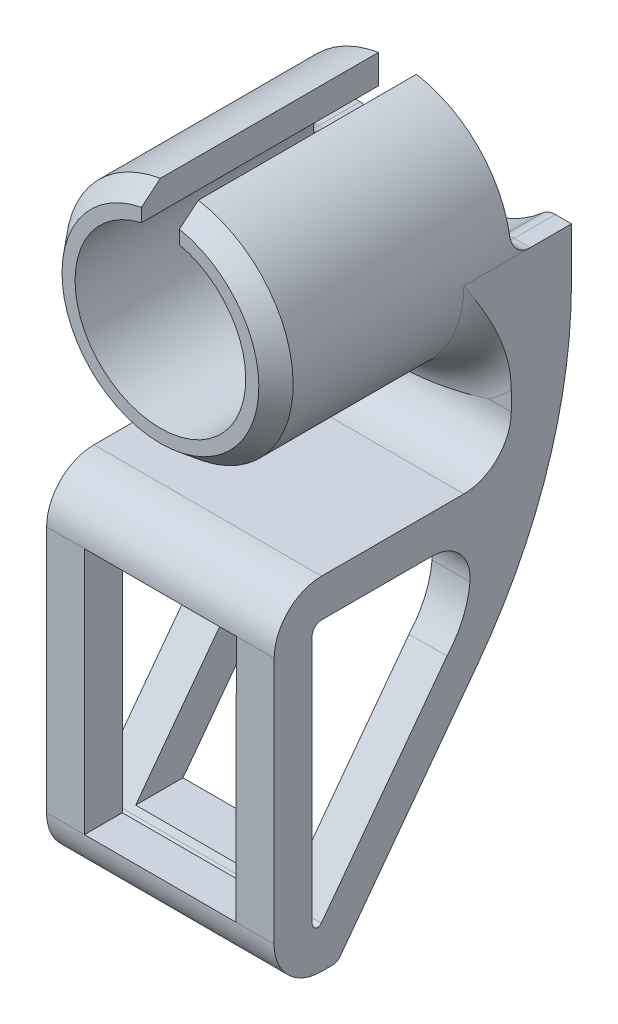
SolidWorks part; units mm, degrees
material "ABS PC"
ref_plane "Front Plane" through (0, 0, 0) normal (0, 0, 1) x (1, 0, 0)
ref_plane "Top Plane" through (0, 0, 0) normal (0, 1, 0) x (1, 0, 0)
ref_plane "Right Plane" through (0, 0, 0) normal (1, 0, 0) x (0, 0, -1)
sketch "Sketch1" plane through (0, 0, 0) normal (0, 0, 1) x (1, 0, 0)
  circle A0 centre (0, 0) radius 12
  dimension "D1" = 24
extrude "Boss-Extrude1" add sketch "Sketch1" along normal blind 25
sketch "Sketch2" plane through (0, 0, 25) normal (0, 0, 1) x (1, 0, 0)
  line L3 (-2, 12) -> (2, 12)
  line L7 (-2, 8.775) -> (-2, 12)
  line L10 (2, 8.775) -> (2, 12)
  arc A0 (-2, 8.775) -> (2, 8.775) centre (0, 0) ccw
  point P1 (0, 12)
  dimension "D1" = 18
  dimension "D4" = 4
  dimension "D6" = 12
extrude "Cut-Extrude1" cut sketch "Sketch2" against normal up to surface (25 mm away) up to face at (12, 0, 0)
sketch "Sketch3" plane through (0, 0, 0) normal (0, 0, -1) x (-1, 0, 0)
  line L0 (-9.5028, 0) -> (-12, 0)
  line L1 (9.5028, 0) -> (12, 0)
  line L2 (12, 0) -> (12, -19)
  line L3 (-12, 0) -> (-12, -19)
  line L4 (12, -19) -> (-12, -19)
  arc A0 (-9.5028, 0) -> (9.5028, 0) centre (0, 9.5) ccw
  circle A1 centre (0, 0) radius 12 construction
  point P11 (0, -3.937)
  dimension "D1" = 19
  dimension "D2" = 13.437
  dimension "D3" = 3.937
extrude "Boss-Extrude2" add sketch "Sketch3" along normal blind 6.35
fillet "Fillet1" radius 7.62 1 edges at (0, -9, 0)
fillet "Fillet2" [suppressed] radius 7.62
chamfer "Chamfer1" distance 2 angle 39 1 edges at (0, -12, 25) first distance on face at (0, 2.526, 8.3333)
sketch "Sketch6" plane through (0, -19, 0) normal (0, -1, 0) x (1, 0, 0)
  line L0 (-12, 25) -> (-12, -6.35)
  line L1 (-12, 25) -> (12, 25)
  line L2 (-12, -6.35) -> (12, -6.35)
  line L3 (12, 25) -> (12, -6.35)
  line L6 (10.3804, 25) -> (-10.3804, 25) construction
  point P1 (0, 0)
  point P9 (0, -6.35)
extrude "Boss-Extrude3" add sketch "Sketch6" along normal blind 3
sketch "Sketch7" plane through (12, 0, 0) normal (1, 0, 0) x (0, 0, -1)
  line L0 (-25, -22) -> (6.35, -22)
  line L2 (6.35, -22) -> (-18.3486, -55.1118)
  line L3 (-25.0132, -55.1118) -> (-18.3486, -55.1118)
  line L4 (-25, -22) -> (-25.0132, -55.1118)
extrude "Boss-Extrude4" add sketch "Sketch7" against normal up to surface (24 mm away) up to face at (-12, -13.6667, 6.2167)
fillet "Fillet3" radius 50 1 edges at (0, -22, -6.35)
fillet "Fillet7" radius 5 2 edges at (0, -19, 0) (0, -12, 0)
fillet "Fillet8" radius 5 1 edges at (0, -55.1118, 25.0132)
fillet "Fillet9" radius 5 1 edges at (0, -19, 25)
sketch "Sketch8" plane through (12, 0, 0) normal (1, 0, 0) x (0, 0, -1)
  line L29 (-5, -23) -> (-20.0008, -23)
  line L30 (-21.0008, -23.9996) -> (-21.0112, -50.1114)
  line L31 (-20.319, -51.0632) -> (-6.7779, -32.9096)
  line L32 (-5, -23) -> (-20.0008, -23)
  line L33 (-21.0008, -23.9996) -> (-21.0112, -50.1114)
  line L34 (-20.319, -51.0632) -> (-6.7779, -32.9096)
  arc A12 (-5, -23) -> (-6.7779, -32.9096) centre (-13.828, -26.5305) cw
  arc A16 (-20.0008, -23) -> (-21.0008, -23.9996) centre (-20.0008, -24) ccw
  arc A17 (-21.0112, -50.1114) -> (-20.319, -51.0632) centre (-20.0112, -50.1118) ccw
  arc A18 (-6.7779, -32.9096) -> (-0.7142, -21.914) centre (-43.65, -5.406) ccw
  arc A19 (-5, -23) -> (-0.7142, -21.914) centre (-5, -14) ccw
  arc A20 (-20.0008, -23) -> (-21.0008, -23.9996) centre (-20.0008, -24) ccw
  arc A21 (-21.0112, -50.1114) -> (-20.319, -51.0632) centre (-20.0112, -50.1118) ccw
  dimension "D1" = 4
extrude "Cut-Extrude2" cut sketch "Sketch8" against normal up to surface (24 mm away) up to face at (-12, -22.5457, 8.155)
fillet "Fillet10" radius 1 1 edges at (0, -55.1118, 18.3486)
fillet "Fillet12" radius 2 2 edges at (-9.5028, 0, -3.175) (9.5028, 0, -3.175)
fillet "Fillet13" radius 2 4 edges at (-9.5981, -0.1265, 0) (-11.1491, 0, 0) (9.5981, -0.1265, 0) (11.1491, 0, 0)
sketch "Sketch9" plane through (0, 0.0099, 24.9913) normal (0, 0.0004, 1) x (1, 0, 0)
  line L0 (12, -24.0079) -> (-12, -24.0079) construction
  line L1 (-8, -50.1197) -> (8, -50.1197)
  line L2 (-8, -50.1197) -> (-8, -24.0079)
  line L3 (-8, -24.0079) -> (8, -24.0079)
  line L4 (8, -50.1197) -> (8, -24.0079)
  line L5 (-12, -50.1197) -> (12, -50.1197) construction
  line L6 (12, -55.1197) -> (-12, -55.1197) construction
  line L7 (-12, -50.1197) -> (-12, -24.0079) construction
  point P7 (0, 0)
  point P9 (0, -55.1197)
  point P12 (0, -24.0079)
  dimension "D1" = 4
extrude "Cut-Extrude3" cut sketch "Sketch9" against normal up to surface (10.3905 mm away) up to face at (0, -45.0054, 10.8102)
fillet "Fillet14" radius 0.5 1 edges at (0, -51.0632, 20.319)
fillet "Fillet15" radius 4 1 edges at (0, -23, 5)
